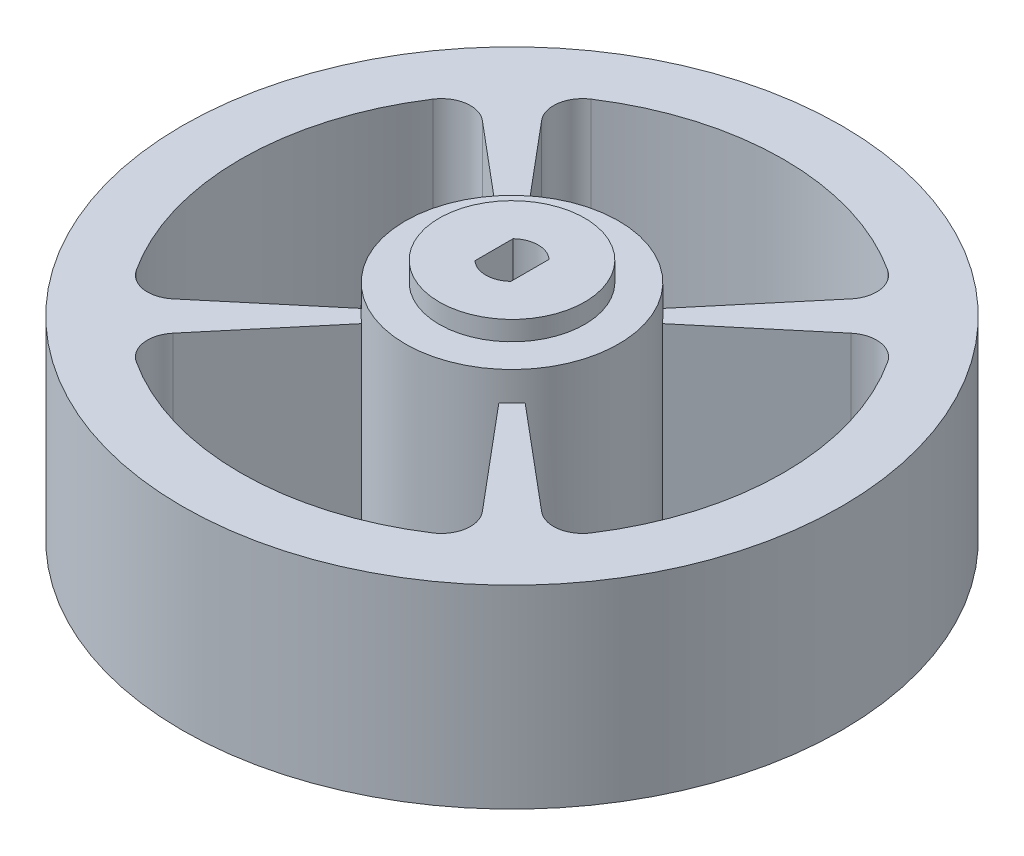
SolidWorks part; units mm, degrees
ref_plane "前视基准面" through (0, 0, 0) normal (0, 0, 1) x (1, 0, 0)
ref_plane "上视基准面" through (0, 0, 0) normal (0, 1, 0) x (1, 0, 0)
ref_plane "右视基准面" through (0, 0, 0) normal (1, 0, 0) x (0, 0, -1)
other "Configuration Table"
sketch "草图1" plane through (0, 0, 0) normal (0, 1, 0) x (1, 0, 0)
  line L0 (-1.85, 1.9666) -> (-1.85, -1.9666)
  line L1 (1.85, 1.9666) -> (1.85, -1.9666)
  circle A0 centre (0, 0) radius 34
  circle A1 centre (0, 0) radius 11
  circle A2 centre (0, 0) radius 7.5
  circle A3 centre (0, 0) radius 2.7
  dimension "D1" = 68
  dimension "D2" = 22
  dimension "D3" = 15
  dimension "D4" = 5.4
  dimension "D5" = 3.7
extrude "凸台-拉伸1" add sketch "草图1" along normal mid plane 20 contours A0 A1 region at (-33.0383, 0, 0)
extrude "凸台-拉伸2" add sketch "草图1<3>" along normal blind 13 contours A1 A2 region at (-10.6889, 0, 0)
sketch "草图1<3>" plane through (0, 0, 0) normal (0, 1, 0) x (1, 0, 0) same geometry as "草图1"
extrude "凸台-拉伸3" add sketch "草图1<4>" along normal blind 15 contours A2 A3 | L1 A3 | L0 A3 region at (-2.1951, 0, 0) region at (2.1951, 0, 0) region at (-7.2879, 0, 0)
sketch "草图1<4>" plane through (0, 0, 0) normal (0, 1, 0) x (1, 0, 0) same geometry as "草图1"
extrude "凸台-拉伸4" add sketch "草图1<6>" against normal up to surface (10 mm away) contours A2 A3 | A1 A2 | L0 A3 | L1 A3 region at (-2.1951, 0, 0) region at (2.1951, 0, 0) region at (-10.6889, 0, 0) region at (-7.2879, 0, 0) up to face at (0, -10, 11)
sketch "草图1<6>" plane through (0, 0, 0) normal (0, 1, 0) x (1, 0, 0) same geometry as "草图1"
sketch "草图2" plane through (0, 10, 0) normal (0, 1, 0) x (1, 0, 0)
  line L0 (0, 0) -> (0, 47.9805) construction
  line L1 (-7.0707, 8.4265) -> (-15.9536, 19.0127)
  line L2 (7.0707, 8.4265) -> (15.9536, 19.0127)
  line L3 (8.4265, -7.0707) -> (19.0127, -15.9536)
  line L4 (8.4265, 7.0707) -> (19.0127, 15.9536)
  line L5 (-7.0707, -8.4265) -> (-15.9536, -19.0127)
  line L6 (7.0707, -8.4265) -> (15.9536, -19.0127)
  line L7 (-8.4265, 7.0707) -> (-19.0127, 15.9536)
  line L8 (-8.4265, -7.0707) -> (-19.0127, -15.9536)
  arc A0 (15.2941, 23.454) -> (-15.2941, 23.454) centre (0, 0) ccw
  arc A1 (7.0707, 8.4265) -> (-7.0707, 8.4265) centre (0, 0) ccw
  arc A2 (15.9536, 19.0127) -> (15.2941, 23.454) centre (13.6554, 20.9411) ccw
  arc A3 (-15.9536, 19.0127) -> (-15.2941, 23.454) centre (-13.6554, 20.9411) cw
  arc A4 (19.0127, -15.9536) -> (23.454, -15.2941) centre (20.9411, -13.6554) ccw
  arc A5 (23.454, -15.2941) -> (23.454, 15.2941) centre (0, 0) ccw
  arc A6 (19.0127, 15.9536) -> (23.454, 15.2941) centre (20.9411, 13.6554) cw
  arc A7 (8.4265, -7.0707) -> (8.4265, 7.0707) centre (0, 0) ccw
  arc A8 (-15.9536, -19.0127) -> (-15.2941, -23.454) centre (-13.6554, -20.9411) ccw
  arc A9 (-15.2941, -23.454) -> (15.2941, -23.454) centre (0, 0) ccw
  arc A10 (15.9536, -19.0127) -> (15.2941, -23.454) centre (13.6554, -20.9411) cw
  arc A11 (-7.0707, -8.4265) -> (7.0707, -8.4265) centre (0, 0) ccw
  arc A12 (-19.0127, 15.9536) -> (-23.454, 15.2941) centre (-20.9411, 13.6554) ccw
  arc A13 (-23.454, 15.2941) -> (-23.454, -15.2941) centre (0, 0) ccw
  arc A14 (-19.0127, -15.9536) -> (-23.454, -15.2941) centre (-20.9411, -13.6554) cw
  arc A15 (-8.4265, 7.0707) -> (-8.4265, -7.0707) centre (0, 0) ccw
  point P38 (0, 0)
  dimension "D3" = 56
  dimension "D4" = 22
  dimension "D5" = 3
  dimension "D6" = 4
  dimension "D1" = 40
  dimension "D2" = 40
extrude "切除-拉伸1" cut sketch "草图2" against normal through all
